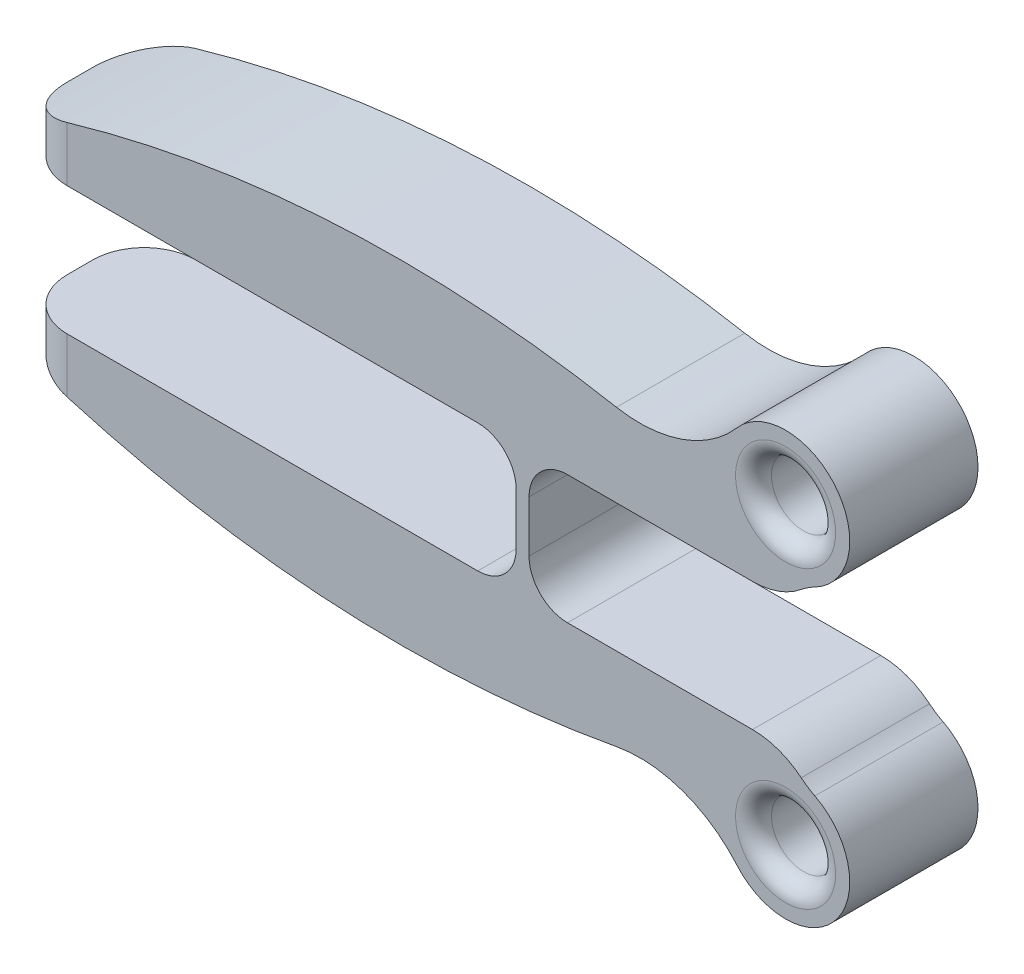
SolidWorks part; units mm, degrees
ref_plane "Front Plane" through (0, 0, 0) normal (0, 0, 1) x (1, 0, 0)
ref_plane "Top Plane" through (0, 0, 0) normal (0, 1, 0) x (1, 0, 0)
ref_plane "Right Plane" through (0, 0, 0) normal (1, 0, 0) x (0, 0, -1)
sketch "Sketch1" plane through (0, 0, 0) normal (0, 0, 1) x (1, 0, 0)
  line L0 (-2.75, -3.3591) -> (-2.75, -0.6091)
  line L6 (0, -0.6091) -> (10, -0.6091)
  line L7 (2.75, -3.3591) -> (2.75, -0.6091)
  line L8 (0, -0.6091) -> (0, 0.8909) construction
  line L13 (0, 0.8909) -> (10, 0.8909) construction
  line L14 (10, -0.6091) -> (10, 0.8909)
  line L15 (0, -0.6091) -> (-20, -0.6091)
  line L16 (0, -0.6091) -> (0, 0.8909)
  line L17 (0, 0.8909) -> (-20, 0.8909) construction
  line L18 (-20, -0.6091) -> (-20, 0.8909)
  line L19 (-0.5, -0.6091) -> (0, -0.6091)
  line L20 (-0.5, -0.6091) -> (-0.5, -3.1091)
  line L21 (-0.5, -3.1091) -> (0, -3.1091)
  line L22 (0, -0.6091) -> (0, -3.1091)
  circle A2 centre (0, -3.3591) radius 2.75
  circle A3 centre (0, -3.3591) radius 1.45
  arc A4 (-20, 0.8909) -> (10, 0.8909) centre (-5, -42.8591) cw
  circle A5 centre (10, 2.642) radius 2.5
  circle A6 centre (10, 2.642) radius 1.25
  point P0 (0, 0)
  point P15 (-5, 3.3909)
  point P24 (0, 0)
  dimension "D3" = 5.5
  dimension "D4" = 2.9
  dimension "D1" = 10
  dimension "D11" = 5
  dimension "D12" = 2.5
  dimension "D2" = 20
  dimension "D5" = 1.5
  dimension "D6" = 3.3591
  dimension "D7" = 2.5
  dimension "D8" = 2.5
  dimension "D9" = 0.5
  dimension "D10" = 10
  dimension "D13" = 3.2511
extrude "Boss-Extrude1" add sketch "Sketch1" along normal blind 5 contours L14 L6 L13 | L22 A3 L20 L21 | A3 L22 A2 L20 | A2 L22 L15 L20 | L14 A5 A4 A6 | L16 L15 L18 L17 | A5 | A6 region at (-5.2404, 1.0698, 0) region at (-0.2514, -1.2816, 0) region at (-0.3752, -0.6229, 0) region at (-0.2469, -2.5235, 0) region at (9.4849, 5.016, 0)
sketch "Sketch2" plane through (0, -0.6091, 0) normal (0, -1, 0) x (1, 0, 0)
  line L0 (10, 5) -> (10, 0)
  line L1 (10, 5) -> (0, 5) construction
  line L3 (10, 0) -> (0, 0) construction
  line L5 (10, 0) -> (0, 0)
  line L6 (10, 5) -> (0, 5)
fillet "Fillet3" radius 2 2 edges at (-20, 0.1409, 0) (-20, 0.1409, 5)
ref_plane "Plane1" through (0, -3.1091, 0) normal (0, -1, 0) x (-1, 0, 0)
fillet "Fillet4" radius 3 1 edges at (10, 0.142, 2.5)
fillet "Fillet5" radius 5 1 edges at (7.7248, 1.6059, 2.5)
mirror "Mirror2" about plane through (0, -3.1091, 0) normal (0, -1, 0) of bodies 101 103
fillet "Fillet6" radius 1.5 4 edges at (-0.5, -5.6091, 2.5) (0, -5.6091, 2.5) (0, -0.6091, 2.5) (-0.5, -0.6091, 2.5)
fillet "Fillet8" radius 0.7 4 edges at (11.25, -8.8603, 0) (11.25, -8.8603, 5) (11.25, 2.642, 0) (11.25, 2.642, 5)
fillet "Fillet9" radius 3 2 edges at (10, -5.6091, 2.5) (10, -0.6091, 2.5)
equation "\"Length\"= 35"
